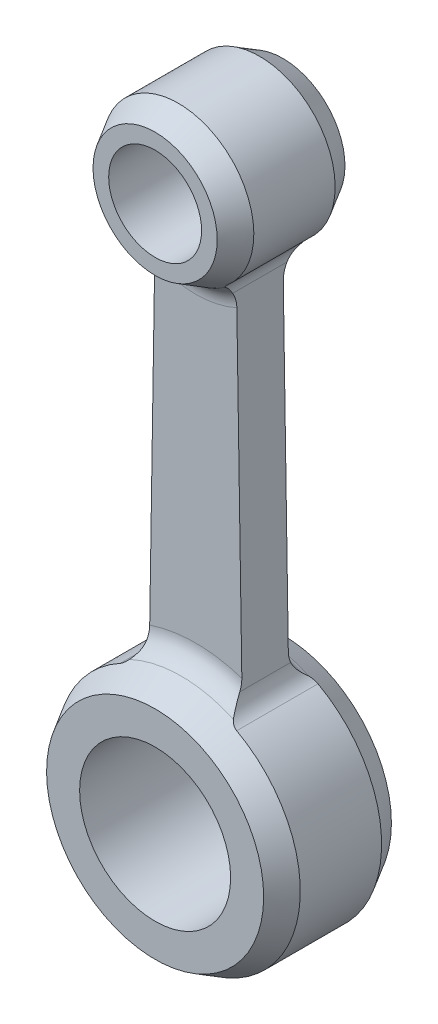
SolidWorks part; units mm, degrees
ref_plane "Plan1" through (0, 0, 0) normal (0, 0, 1) x (1, 0, 0)
ref_plane "Plan2" through (0, 0, 0) normal (0, 1, 0) x (1, 0, 0)
ref_plane "Plan3" through (0, 0, 0) normal (1, 0, 0) x (0, 0, -1)
sketch "Esquisse1" plane through (0, 0, 0) normal (0, 0, 1) x (1, 0, 0)
  line L0 (0, 47) -> (0, 0) construction
  line L1 (-3.5, 41.5228) -> (-4, 9.7082)
  line L2 (3.5, 41.5228) -> (4, 9.7082)
  circle A0 centre (0, 0) radius 6.5
  arc A1 (-4, 9.7082) -> (4, 9.7082) centre (0, 0) ccw
  circle A2 centre (0, 47) radius 4
  arc A3 (3.5, 41.5228) -> (-3.5, 41.5228) centre (0, 47) ccw
  dimension "D1" = 13
  dimension "D2" = 8
  dimension "D3" = 21
  dimension "D4" = 13
  dimension "D5" = 47
  dimension "D6" = 3.5
  dimension "D7" = 4
extrude "Base-Extrusion" add sketch "Esquisse1" along normal blind 4
sketch "Esquisse2" plane through (0, 0, 4) normal (0, 0, 1) x (1, 0, 0)
  circle A0 centre (0, 47) radius 6.5
  circle A1 centre (0, 47) radius 4
  circle A2 centre (0, 0) radius 10.5
  circle A3 centre (0, 0) radius 6.5
  dimension "D1" = 13
  dimension "D2" = 21
extrude "Boss.-Extru.1" add sketch "Esquisse2" along normal blind 3.5
sketch "Esquisse3" plane through (0, 0, 0) normal (0, 0, -1) x (-1, 0, 0)
  circle A0 centre (0, 47) radius 6.5
  circle A1 centre (0, 47) radius 4
  circle A2 centre (0, 0) radius 6.5
  circle A3 centre (0, 0) radius 10.5
  dimension "D1" = 13
  dimension "D2" = 21
extrude "Boss.-Extru.2" add sketch "Esquisse3" along normal blind 3.5
fillet "Congé1" radius 2 8 edges at (0, 40.5, 4) (0, 10.5, 4) (0, 40.5, 0) (0, 10.5, 0) (3.5, 41.5228, 2) (4, 9.7082, 2) (-4, 9.7082, 2) (-3.5, 41.5228, 2)
chamfer "Chanfrein1" distance 2 angle 30 12 edges at (6.5, 47, 7.5) (10.5, 0, 7.5) (-6.5, 47, -3.5) (-10.5, 0, -3.5) (0, 40.5, -2) (0, 40.5, 6) (0, 10.5, 6) (0, 10.5, -2) (-3.6648, 41.2902, -0.9714) (-3.6648, 41.2902, 4.9714) (4.0958, 10.307, 4.5807) (-4.0958, 10.307, 4.5807)
ref_plane "Plan4" through (0, 0, 2) normal (0, 0, -1) x (-1, 0, 0)
ref_plane "Plan6" through (0, 0, 2) normal (0, 0, 1) x (1, 0, 0)
